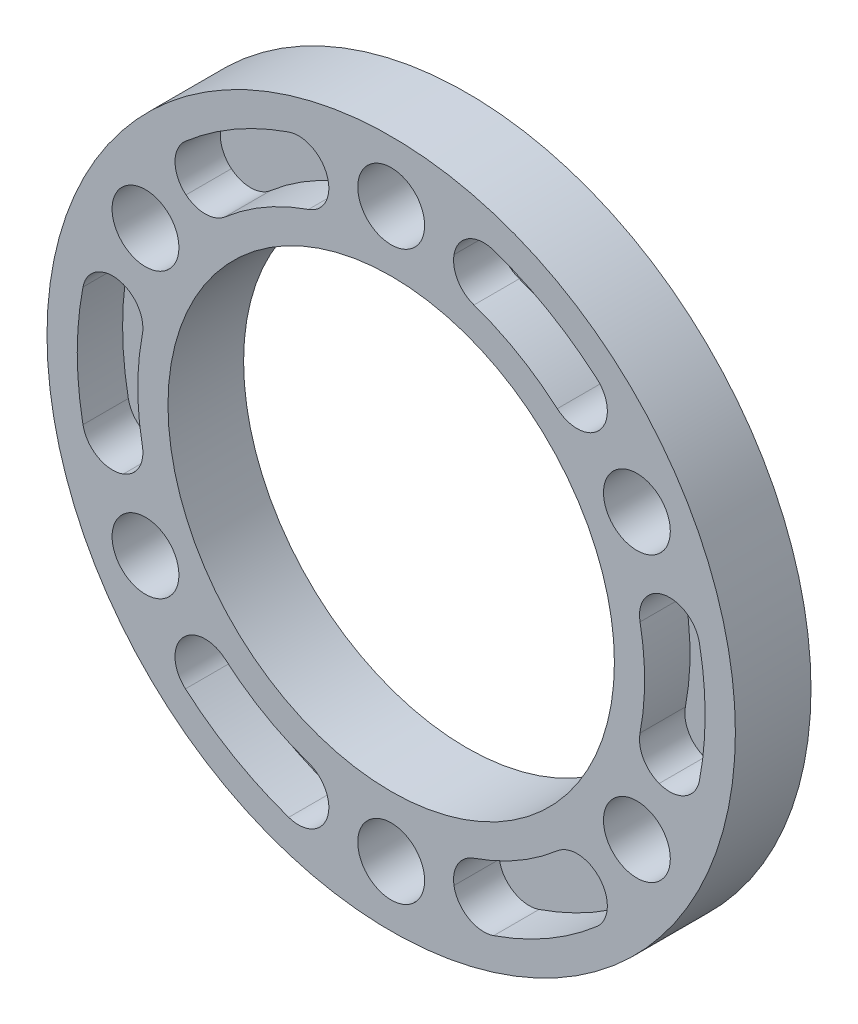
SolidWorks part; units mm, degrees
material "ABS"
ref_plane "Front Plane" through (0, 0, 0) normal (0, 0, 1) x (1, 0, 0)
ref_plane "Top Plane" through (0, 0, 0) normal (0, 1, 0) x (1, 0, 0)
ref_plane "Right Plane" through (0, 0, 0) normal (1, 0, 0) x (0, 0, -1)
sketch "Sketch1" plane through (0, 0, 0) normal (0, 0, 1) x (1, 0, 0)
  circle A0 centre (0, 0) radius 23.8252 construction
  circle A1 centre (0, 23.8252) radius 2.8067
  circle A2 centre (20.6332, 11.9126) radius 2.8067
  circle A3 centre (20.6332, -11.9126) radius 2.8067
  circle A4 centre (0, -23.8252) radius 2.8067
  circle A5 centre (-20.6332, -11.9126) radius 2.8067
  circle A6 centre (-20.6332, 11.9126) radius 2.8067
  circle A7 centre (0, 0) radius 18.7452
  circle A8 centre (0, 0) radius 28.9052
  point P17 (0, 0)
  dimension "D1" = 47.6504
  dimension "D2" = 5.6134
  dimension "D4" = 5.08
  dimension "D5" = 5.08
  dimension "D3" = 6
extrude "Boss-Extrude1" add sketch "Sketch1" along normal blind 6.35
shell "Shell1" thickness 2.54 removed face at (-17.8265, -11.9126, 6.35)
fillet "Fillet1" radius 2.54 24 edges at (20.2425, -6.5802, 4.445) (24.8943, -8.683, 4.445) (24.8943, 8.683, 4.445) (20.2425, 6.5802, 4.445) (4.9274, -25.9007, 4.445) (4.4227, -20.8207, 4.445) (15.8199, -14.2405, 4.445) (19.9669, -17.2176, 4.445) (-4.9274, -25.9007, 4.445) (-4.4227, -20.8207, 4.445) (-19.9669, -17.2176, 4.445) (-15.8199, -14.2405, 4.445) (-24.8943, -8.683, 4.445) (-20.2425, -6.5802, 4.445) (-24.8943, 8.683, 4.445) (-20.2425, 6.5802, 4.445) (-19.9669, 17.2176, 4.445) (-15.8199, 14.2405, 4.445) (-4.4227, 20.8207, 4.445) (-4.9274, 25.9007, 4.445) (4.4227, 20.8207, 4.445) (4.9274, 25.9007, 4.445) (15.8199, 14.2405, 4.445) (19.9669, 17.2176, 4.445)
